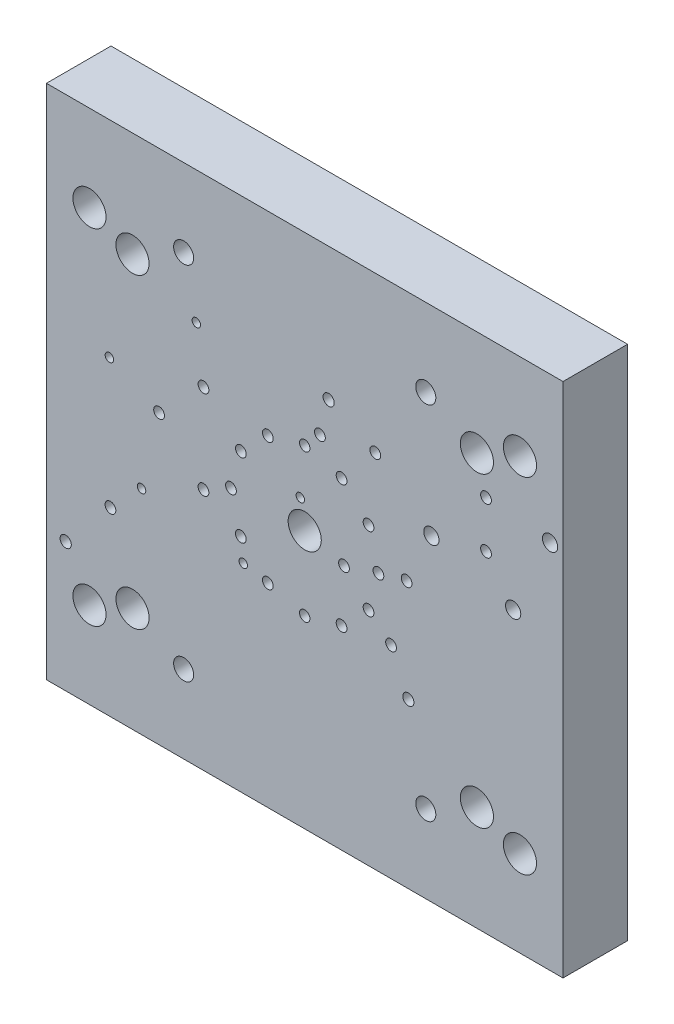
SolidWorks part; units mm, degrees
ref_plane "Front Plane" through (0, 0, 0) normal (0, 0, 1) x (1, 0, 0)
ref_plane "Top Plane" through (0, 0, 0) normal (0, 1, 0) x (1, 0, 0)
ref_plane "Right Plane" through (0, 0, 0) normal (1, 0, 0) x (0, 0, -1)
sketch "Sketch1" plane through (0, 0, 0) normal (0, 0, 1) x (1, 0, 0)
  line L1 (-152.4, 152.4) -> (152.4, 152.4)
  line L2 (-152.4, 152.4) -> (-152.4, -152.4)
  line L3 (-152.4, -152.4) -> (152.4, -152.4)
  line L4 (152.4, 152.4) -> (152.4, -152.4)
  line L5 (-152.4, 152.4) -> (152.4, -152.4) construction
  line L6 (-152.4, -152.4) -> (152.4, 152.4) construction
  point P0 (0, 0)
  dimension "D1" = 304.8
  dimension "D2" = 304.8
extrude "Boss-Extrude1" add sketch "Sketch1" along normal blind 38.1
sketch "Sketch2" plane through (0, 0, 38.1) normal (0, 0, 1) x (1, 0, 0)
  line L0 (-152.4, 0) -> (152.4, 0) construction
  line L5 (-152.4, 152.4) -> (-152.4, -152.4) construction
  line L6 (152.4, -152.4) -> (152.4, 152.4) construction
  line L7 (-152.4, -101.6) -> (152.4, -101.6) construction
  line L8 (-152.4, 101.6) -> (152.4, 101.6) construction
  line L9 (0, 101.6) -> (0, -101.6) construction
  line L10 (127, 101.6) -> (127, -101.6) construction
  line L11 (-127, 101.6) -> (-127, -101.6) construction
  circle A0 centre (-127, 101.6) radius 6.5151
  circle A1 centre (127, 101.6) radius 6.5151
  circle A2 centre (127, -101.6) radius 6.5151
  circle A3 centre (-127, -101.6) radius 6.5151
  circle A4 centre (0, 0) radius 6.5151
  dimension "D5" = 13.0302
  dimension "D1" = 101.6
  dimension "D2" = 101.6
  dimension "D3" = 127
  dimension "D4" = 127
extrude "HAAS T-Slot Holes" cut sketch "Sketch2" against normal through all
sketch "Sketch3" plane through (0, 0, 38.1) normal (0, 0, 1) x (1, 0, 0)
  circle A0 centre (-127, 101.6) radius 9.779
  circle A1 centre (127, 101.6) radius 9.779
  circle A2 centre (0, 0) radius 9.779
  circle A3 centre (127, -101.6) radius 9.779
  circle A4 centre (-127, -101.6) radius 9.779
  dimension "D1" = 19.558
extrude "HAAS Counter Bores" cut sketch "Sketch3" against normal offset from surface (22.225 mm away) 15.875 contours A0 | A1 | A2 | A3 | A4 up to face at (6.5151, 0, 0)
sketch "Sketch4" plane through (0, 0, 38.1) normal (0, 0, 1) x (1, 0, 0)
  line L0 (-127, 90.4875) -> (127, 90.4875) construction
  line L1 (-127, 30.1625) -> (127, 30.1625) construction
  line L2 (-127, 30.1625) -> (-127, -30.1625) construction
  line L3 (-127, -30.1625) -> (127, -30.1625) construction
  line L4 (127, 30.1625) -> (127, -30.1625) construction
  line L5 (-127, 30.1625) -> (127, -30.1625) construction
  line L6 (-127, -30.1625) -> (127, 30.1625) construction
  line L7 (-127, -90.4875) -> (127, -90.4875) construction
  line L8 (-101.6, 90.4875) -> (-101.6, 84.1375) construction
  line L9 (-101.6, -90.4875) -> (-101.6, -84.1375) construction
  line L10 (101.6, -90.4875) -> (101.6, -84.1375) construction
  line L11 (101.6, 90.4875) -> (101.6, 84.1375) construction
  circle A0 centre (-101.6, 90.4875) radius 6.5151
  circle A1 centre (101.6, 90.4875) radius 6.5151
  circle A2 centre (-101.6, -90.4875) radius 6.5151
  circle A3 centre (101.6, -90.4875) radius 6.5151
  point P0 (0, 0)
  dimension "D9" = 13.0302
  dimension "D1" = 60.325
  dimension "D2" = 254
  dimension "D5" = 203.2
  dimension "D6" = 25.4
  dimension "D7" = 203.2
  dimension "D8" = 6.35
  dimension "D3" = 60.325
  dimension "D4" = 60.325
extrude "Tormach T-Slot Holes" cut sketch "Sketch4" against normal through all
sketch "Sketch5" plane through (0, 0, 38.1) normal (0, 0, 1) x (1, 0, 0)
  circle A0 centre (-101.6, 90.4875) radius 9.779
  circle A1 centre (101.6, 90.4875) radius 9.779
  circle A2 centre (101.6, -90.4875) radius 9.779
  circle A3 centre (-101.6, -90.4875) radius 9.779
  dimension "D1" = 19.558
extrude "Tormach Counter bores" cut sketch "Sketch5" against normal up to surface (22.225 mm away) up to face at (-117.221, 101.6, 15.875)
sketch "Sketch6" plane through (0, 0, 38.1) normal (0, 0, 1) x (1, 0, 0)
  circle A0 centre (0, 0) radius 43.5 construction
  circle A1 centre (0, 43.5) radius 3.0734
  circle A2 centre (0, -43.5) radius 3.0734
  dimension "D1" = 87.0001
  dimension "D2" = 6.1468
extrude "Sprocket Locating Holes" cut sketch "Sketch6" against normal blind 6.35
sketch "Sketch7" plane through (0, 0, 38.1) normal (0, 0, 1) x (1, 0, 0)
  circle A0 centre (0, 0) radius 43.5 construction
  circle A2 centre (43.5, 0) radius 3.175
  circle A4 centre (37.6721, -21.75) radius 3.175
  circle A5 centre (21.75, -37.6721) radius 3.175
  circle A6 centre (0, -43.5) radius 3.175 [skipped]
  circle A7 centre (-21.75, -37.6721) radius 3.175
  circle A8 centre (-37.6721, -21.75) radius 3.175
  circle A9 centre (-43.5, 0) radius 3.175
  circle A10 centre (-37.6721, 21.75) radius 3.175
  circle A11 centre (-21.75, 37.6721) radius 3.175
  circle A12 centre (0, 43.5) radius 3.175 [skipped]
  circle A13 centre (21.75, 37.6721) radius 3.175
  circle A14 centre (37.6721, 21.75) radius 3.175
  point P31 (0, 0)
  dimension "D1" = 87.0001
  dimension "D2" = 6.35
  dimension "D3" = 12
extrude "Sprocket Mounting clearance holes" cut sketch "Sketch7" against normal blind 9.525
sketch "Sketch8" plane through (0, 0, 38.1) normal (0, 0, 1) x (1, 0, 0)
  line L1 (-71.4375, 106.4641) -> (71.4375, 106.4641) construction
  line L2 (-71.4375, 106.4641) -> (-71.4375, -106.4641) construction
  line L3 (-71.4375, -106.4641) -> (71.4375, -106.4641) construction
  line L4 (71.4375, 106.4641) -> (71.4375, -106.4641) construction
  line L5 (-71.4375, 106.4641) -> (71.4375, -106.4641) construction
  line L6 (-71.4375, -106.4641) -> (71.4375, 106.4641) construction
  circle A0 centre (-71.4375, 106.4641) radius 5.9182
  circle A1 centre (71.4375, 106.4641) radius 5.9182
  circle A2 centre (71.4375, -106.4641) radius 5.9182
  circle A3 centre (-71.4375, -106.4641) radius 5.9182
  point P0 (0, 0)
  dimension "D3" = 11.8364
  dimension "D1" = 142.875
  dimension "D2" = 212.9282
extrude "1/2-13 Tapped Holes" cut sketch "Sketch8" against normal blind 19.05
sketch "Sketch9" plane through (0, 0, 38.1) normal (0, 0, 1) x (1, 0, 0)
  circle A8 centre (106.976, 70.3959) radius 3.175
  circle A9 centre (106.976, 42.9004) radius 3.175
  circle A21 centre (8.9855, 53.4682) radius 3.175
  circle A22 centre (41.6559, 60.6579) radius 3.175
  circle A24 centre (-59.7336, 43.5155) radius 3.175
  circle A25 centre (-85.9274, 17.3217) radius 3.175
  circle A26 centre (-59.7336, -8.872) radius 3.175
  circle A27 centre (-114.6339, -45.5104) radius 3.175
  circle A28 centre (-141.0276, -76.0847) radius 3.3
  circle A29 centre (61.1481, -55.6423) radius 3.3
  circle A30 centre (23.1743, -6.3194) radius 3.175
  circle A31 centre (60.143, 4.4124) radius 3.175
  circle A32 centre (50.9527, -32.9693) radius 3.175
  circle A33 centre (-36.2641, -34.7869) radius 2.5
  circle A34 centre (-96.2801, -26.6155) radius 2.5
  circle A35 centre (-115.245, 30.9087) radius 2.5
  circle A36 centre (-63.9656, 74.3148) radius 2.5
  circle A37 centre (-2.6104, 15.5731) radius 2.5
  circle A38 centre (14.1282, 73.9143) radius 3.3
  circle A39 centre (74.7377, 34.7006) radius 4.5
  circle A40 centre (144.7765, 66.2459) radius 4.5
  circle A41 centre (122.9919, 21.0885) radius 4.5
extrude "Cut-Extrude1" cut sketch "Sketch9" against normal blind 19.05
